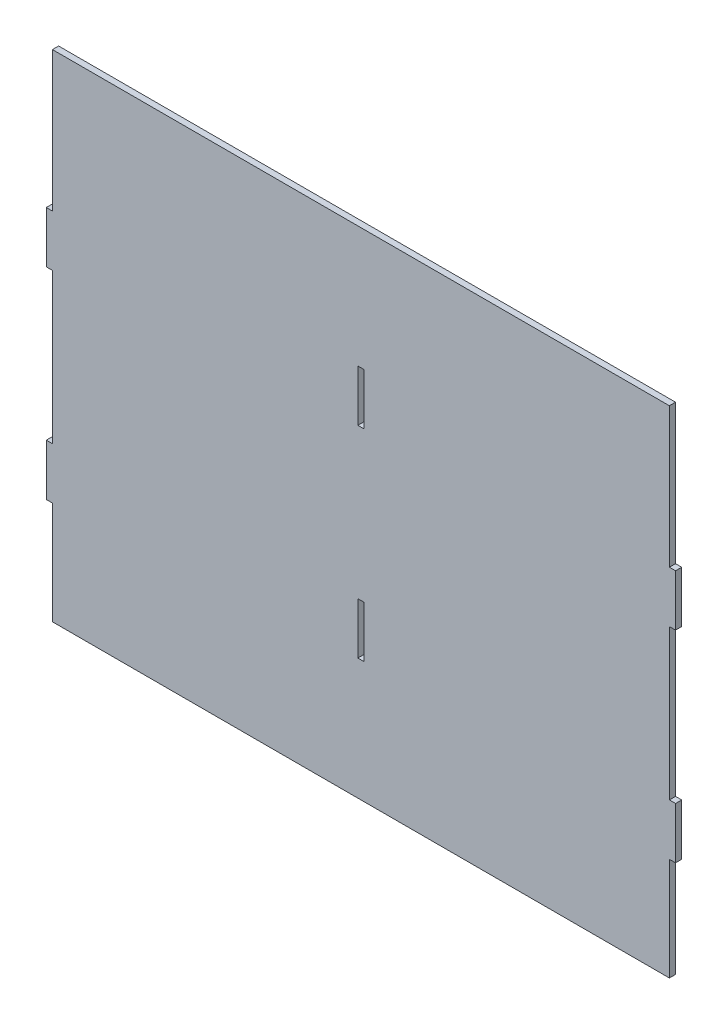
SolidWorks part; units mm, degrees
material "Maple"
ref_plane "Front Plane" through (0, 0, 0) normal (0, 0, 1) x (1, 0, 0)
ref_plane "Top Plane" through (0, 0, 0) normal (0, 1, 0) x (1, 0, 0)
ref_plane "Right Plane" through (0, 0, 0) normal (1, 0, 0) x (0, 0, -1)
sketch "Sketch1" plane through (0, 0, 0) normal (0, 0, 1) x (1, 0, 0)
  line L1 (-300, 241) -> (300, 241)
  line L2 (-300, 241) -> (-300, 105)
  line L3 (-300, -241) -> (300, -241)
  line L4 (300, 241) -> (300, 105)
  line L5 (-300, 241) -> (300, -241) construction
  line L6 (-300, -241) -> (300, 241) construction
  line L7 (-306, 105) -> (-300, 105)
  line L8 (-306, 105) -> (-306, 55)
  line L9 (-306, 55) -> (-300, 55)
  line L11 (-300, 198) -> (-282.5, 173) construction
  line L12 (-300, -141) -> (-300, -241)
  line L13 (0, 98) -> (0, 241) construction
  line L14 (306, 55) -> (300, 55)
  line L15 (306, 105) -> (306, 55)
  line L16 (306, 105) -> (300, 105)
  line L22 (-306, -141) -> (-300, -141)
  line L27 (-3, 123) -> (3, 123)
  line L28 (-3, 123) -> (-3, 73)
  line L29 (-3, 73) -> (3, 73)
  line L30 (3, 123) -> (3, 73)
  line L31 (-3, 123) -> (3, 73) construction
  line L32 (-3, 73) -> (3, 123) construction
  line L40 (0, 98) -> (0, -241) construction
  line L41 (306, -141) -> (300, -141)
  line L44 (300, -141) -> (300, -241)
  line L45 (0, 0) -> (300, 0) construction
  line L46 (-3, -73) -> (3, -73)
  line L47 (3, -123) -> (3, -73)
  line L48 (-3, -123) -> (3, -123)
  line L49 (-3, -123) -> (-3, -73)
  line L50 (-306, -141) -> (-306, -91)
  line L51 (-306, -91) -> (-300, -91)
  line L52 (-300, -91) -> (-300, 55)
  line L53 (306, -141) -> (306, -91)
  line L54 (306, -91) -> (300, -91)
  line L56 (300, 55) -> (300, -91)
  point P0 (0, 0)
  point P6 (-300, 198)
  point P12 (0, 98)
  point P31 (-156.1598, -207)
  dimension "D1" = 600
  dimension "D2" = 50
  dimension "D3" = 136
  dimension "D4" = 6
  dimension "D5" = 50
  dimension "D6" = 50
  dimension "D7" = 100
  dimension "D8" = 118
  dimension "D9" = 50
  dimension "D10" = 6
  dimension "D11" = 50
  dimension "D12" = 6
  dimension "D13" = 6
  dimension "D14" = 146
  dimension "D15" = 6
  dimension "D16" = 146
  dimension "D17" = 100
  dimension "D18" = 136
  dimension "D19" = 118
extrude "Boss-Extrude1" add sketch "Sketch1" along normal blind 6
